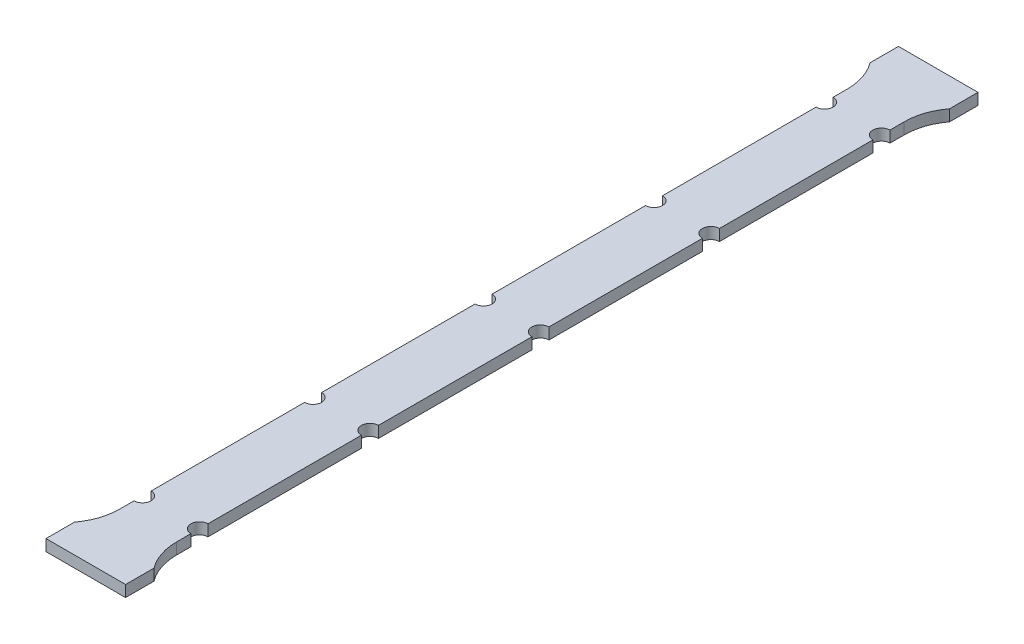
SolidWorks part; units mm, degrees
ref_plane "前视基准面" through (0, 0, 0) normal (0, 0, 1) x (1, 0, 0)
ref_plane "上视基准面" through (0, 0, 0) normal (0, 1, 0) x (1, 0, 0)
ref_plane "右视基准面" through (0, 0, 0) normal (1, 0, 0) x (0, 0, -1)
other "Configuration Table"
sketch "草图1" plane through (0, 0, 0) normal (0, 1, 0) x (1, 0, 0)
  line L0 (0, 0) -> (0, -150)
  line L1 (0, -150) -> (10, -150)
  line L2 (10, -150) -> (10, 0)
  line L3 (10, 0) -> (0, 0)
  line L4 (10, -75) -> (0, -75)
  line L5 (5, -75) -> (7.5, -75)
  line L6 (7.5, -75) -> (7.5, -72.5)
  line L7 (7.5, -72.5) -> (2.5, -72.5)
  line L8 (2.5, -72.5) -> (2.5, -77.5)
  line L9 (2.5, -77.5) -> (7.5, -77.5)
  line L10 (7.5, -77.5) -> (7.5, -75)
  line L19 (10, -150) -> (12, -150)
  line L20 (12, -150) -> (12, -145)
  line L21 (12, -145) -> (10, -145)
  line L22 (10, -145) -> (10, -150)
  line L23 (0, -150) -> (-2, -150)
  line L24 (-2, -150) -> (-2, -145)
  line L25 (-2, -145) -> (0, -145)
  line L26 (0, -145) -> (0, -150)
  line L27 (10, -5) -> (12, -5)
  line L28 (12, -5) -> (12, 0)
  line L29 (12, 0) -> (10, 0)
  line L30 (10, 0) -> (10, -5)
  line L31 (0, -5) -> (-2, -5)
  line L32 (-2, -5) -> (-2, 0)
  line L33 (-2, 0) -> (0, 0)
  line L34 (0, 0) -> (0, -5)
  circle A0 centre (10, -75) radius 1.5
  circle A2 centre (10, -45) radius 1.5
  circle A3 centre (10, -15) radius 1.5
  circle A4 centre (0, -45) radius 1.5
  circle A5 centre (0, -15) radius 1.5
  circle A14 centre (0, -75) radius 1.5
  circle A15 centre (0, -105) radius 1.5
  circle A16 centre (0, -135) radius 1.5
  circle A17 centre (10, -105) radius 1.5
  circle A18 centre (10, -135) radius 1.5
  circle A20 centre (0, -75) radius 1.5
  dimension "D1" = 3
  dimension "D5" = 2
  dimension "D2" = 2
  dimension "D3" = 2
  dimension "D4" = 3
extrude "凸台-拉伸1" add sketch "草图1" along normal blind 2
fillet "圆角1" radius 10 4 edges at (10, 1, 145) (0, 1, 145) (0, 1, 5) (10, 1, 5)
